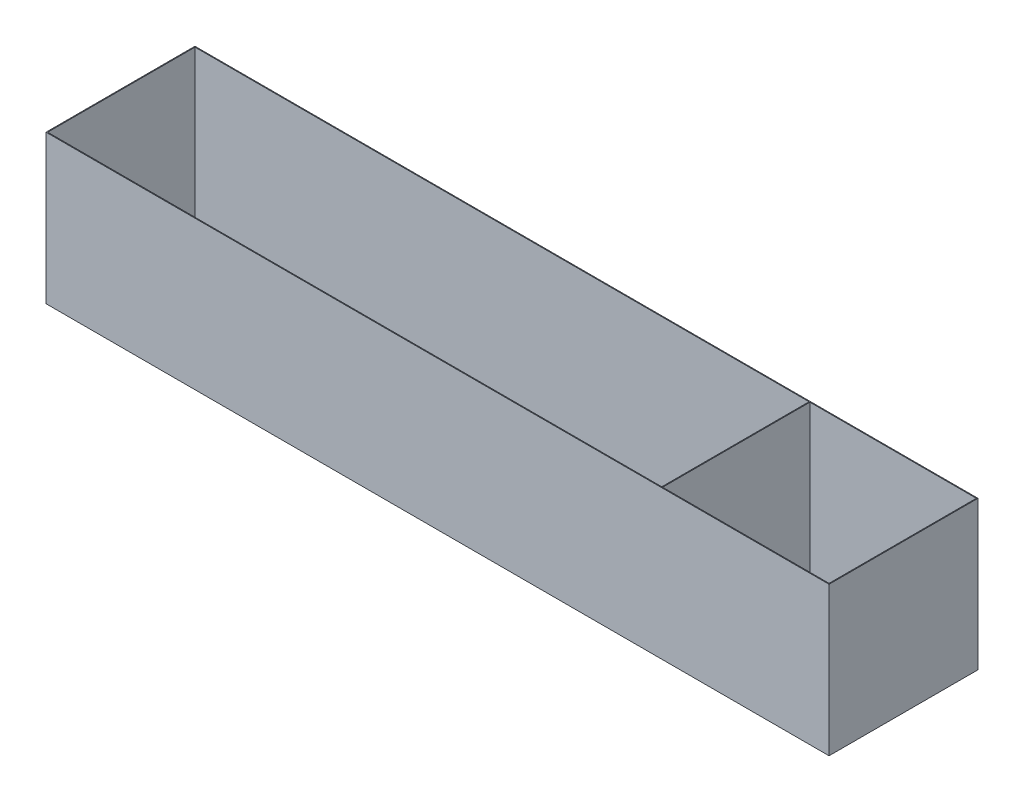
SolidWorks part; units mm, degrees
ref_plane "Front Plane" through (0, 0, 0) normal (0, 0, 1) x (1, 0, 0)
ref_plane "Top Plane" through (0, 0, 0) normal (0, 1, 0) x (1, 0, 0)
ref_plane "Right Plane" through (0, 0, 0) normal (1, 0, 0) x (0, 0, -1)
sketch "Sketch1" plane through (0, 0, 0) normal (0, 1, 0) x (1, 0, 0)
  line L0 (9436.1, 2298.7) -> (9436.1, 50.8) construction
  line L1 (9423.4, 2298.7) -> (9423.4, 50.8) construction
  line L2 (9436.1, 2298.7) -> (9436.1, 50.8)
  line L3 (9423.4, 2298.7) -> (9423.4, 50.8)
  line L4 (11976.1, 50.8) -> (11976.1, 2298.7)
  line L5 (50.8, 50.8) -> (11976.1, 50.8)
  line L6 (50.8, 2298.7) -> (50.8, 50.8)
  line L7 (11976.1, 2298.7) -> (50.8, 2298.7)
  line L8 (11976.1, 50.8) -> (11976.1, 2298.7)
  line L9 (50.8, 50.8) -> (11976.1, 50.8)
  line L10 (50.8, 2298.7) -> (50.8, 50.8)
  line L11 (11976.1, 2298.7) -> (50.8, 2298.7)
  line L12 (38.1, 38.1) -> (11988.8, 38.1)
  line L13 (11988.8, 38.1) -> (11988.8, 2311.4)
  line L14 (11988.8, 2311.4) -> (38.1, 2311.4)
  line L15 (38.1, 2311.4) -> (38.1, 38.1)
  line L16 (38.1, 38.1) -> (11988.8, 38.1)
  line L17 (11988.8, 38.1) -> (11988.8, 2311.4)
  line L18 (11988.8, 2311.4) -> (38.1, 2311.4)
  line L19 (38.1, 2311.4) -> (38.1, 38.1)
  dimension "D1" = 0
  dimension "D2" = 0
extrude "Boss-Extrude1" add sketch "Sketch1" along normal up to surface (2266.95 mm away) contours L18 L19 L16 L17 L11 L8 L9 L10 | L2 L11 L3 L9 region at (9429.75, 0, -1174.75) region at (50.265, 0, -1174.75)
